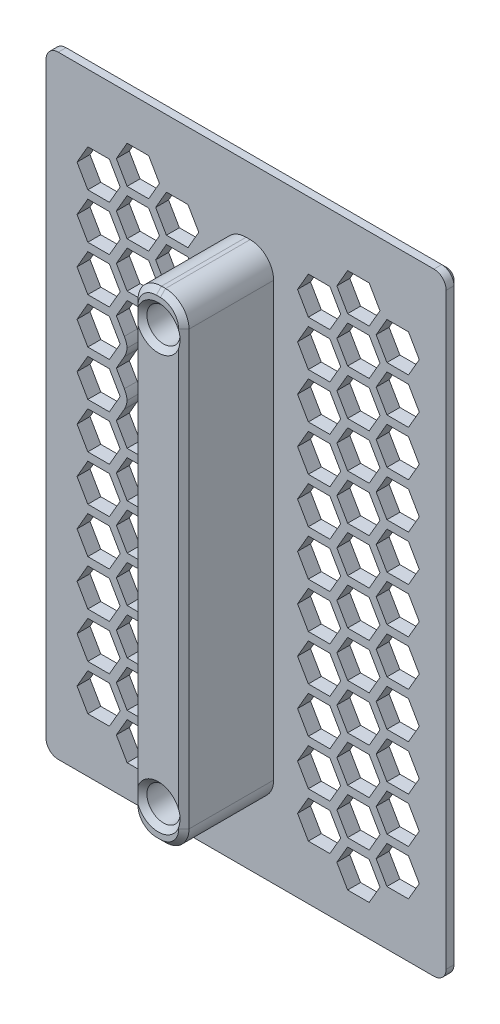
SolidWorks part; units mm, degrees
ref_plane "Front Plane" through (0, 0, 0) normal (0, 0, 1) x (1, 0, 0)
ref_plane "Top Plane" through (0, 0, 0) normal (0, 1, 0) x (1, 0, 0)
ref_plane "Right Plane" through (0, 0, 0) normal (1, 0, 0) x (0, 0, -1)
sketch "Sketch1" plane through (0, 0, 0) normal (0, 0, 1) x (1, 0, 0)
  line L0 (24.5, 37.5) -> (-24.5, 37.5) construction
  line L1 (24.5, -37.5) -> (-24.5, -37.5)
  line L2 (24.5, -37.5) -> (24.5, 37.5)
  line L3 (24.5, 37.5) -> (-24.5, 37.5)
  line L4 (-24.5, -37.5) -> (-24.5, 37.5)
  line L5 (24.5, -37.5) -> (-24.5, 37.5) construction
  line L6 (24.5, 37.5) -> (-24.5, -37.5) construction
  line L7 (24.5, 37.5) -> (24.5, -37.5) construction
  point P0 (0, 0)
extrude "Boss-Extrude1" add sketch "Sketch1" along normal blind 1.5875
sketch "Sketch2" plane through (0, 0, 1.5875) normal (0, 0, 1) x (1, 0, 0)
  line L12 (0.5, 29.5) -> (0, 29.5) construction
  line L13 (-3, 26.5) -> (-3, -26.5) construction
  line L14 (3.5, -26.5) -> (3.5, 26.5) construction
  line L15 (0, -29.5) -> (0.5, -29.5) construction
  line L16 (0.5, 29.5) -> (0, 29.5)
  line L17 (-3, 26.5) -> (-3, -26.5)
  line L18 (3.5, -26.5) -> (3.5, 26.5)
  line L19 (0, -29.5) -> (0.5, -29.5)
  line L20 (-2.873, 26.5) -> (-2.873, -26.5)
  line L21 (0, -29.373) -> (0.5, -29.373)
  line L22 (3.373, -26.5) -> (3.373, 26.5)
  line L23 (0.5, 29.373) -> (0, 29.373)
  arc A12 (3.5, 26.5) -> (0.5, 29.5) centre (0.5, 26.5) ccw construction
  arc A13 (0, 29.5) -> (-3, 26.5) centre (0, 26.5) ccw construction
  arc A14 (0.5, -29.5) -> (3.5, -26.5) centre (0.5, -26.5) ccw construction
  arc A15 (-3, -26.5) -> (0, -29.5) centre (0, -26.5) ccw construction
  arc A16 (3.5, 26.5) -> (0.5, 29.5) centre (0.5, 26.5) ccw
  arc A17 (0, 29.5) -> (-3, 26.5) centre (0, 26.5) ccw
  arc A18 (0.5, -29.5) -> (3.5, -26.5) centre (0.5, -26.5) ccw
  arc A19 (-3, -26.5) -> (0, -29.5) centre (0, -26.5) ccw
  arc A20 (0, 29.373) -> (-2.873, 26.5) centre (0, 26.5) ccw
  arc A21 (-2.873, -26.5) -> (0, -29.373) centre (0, -26.5) ccw
  arc A22 (0.5, -29.373) -> (3.373, -26.5) centre (0.5, -26.5) ccw
  arc A23 (3.373, 26.5) -> (0.5, 29.373) centre (0.5, 26.5) ccw
  dimension "D1" = 0.127
extrude "Boss-Extrude2" add sketch "Sketch2" along normal up to surface (11 mm away) contours L22 A23 L23 A20 L20 A21 L21 A22 region at (0.25, 0, 1.5875)
sketch "Sketch3" plane through (0, 0, 12.5875) normal (0, 0, 1) x (1, 0, 0)
  line L1 (0.25, 25.4) -> (0.25, -25.4) construction
  line L3 (-2.873, 0) -> (3.373, 0) construction
  line L4 (-2.873, -26.5) -> (-2.873, 26.5) construction
  line L5 (3.373, 26.5) -> (3.373, -26.5) construction
  circle A0 centre (0.25, 25.4) radius 2.032
  circle A1 centre (0.25, -25.4) radius 2.032
  point P13 (0.25, 0)
  dimension "D1" = 4.064
  dimension "D2" = 50.8
extrude "Cut-Extrude1" cut sketch "Sketch3" against normal blind 9.525
fillet "Fillet1" radius 1.5 4 edges at (24.5, -37.5, 0.7937) (-24.5, -37.5, 0.7937) (-24.5, 37.5, 0.7937) (24.5, 37.5, 0.7937)
sketch "Sketch4" plane through (0, 0, 0) normal (0, 0, -1) x (-1, 0, 0)
  line L0 (-18.5619, -28.5679) -> (-13.75, -31.346) construction
  line L1 (-16.3896, -31.346) -> (-15.0698, -33.632)
  line L2 (-15.0698, -33.632) -> (-12.4302, -33.632)
  line L3 (-12.4302, -33.632) -> (-11.1104, -31.346)
  line L4 (-11.1104, -31.346) -> (-12.4302, -29.06)
  line L5 (-12.4302, -29.06) -> (-15.0698, -29.06)
  line L6 (-15.0698, -29.06) -> (-16.3896, -31.346)
  line L7 (-21.2015, -28.5679) -> (-19.8817, -30.8539)
  line L8 (-19.8817, -30.8539) -> (-17.242, -30.8539)
  line L9 (-17.242, -30.8539) -> (-15.9222, -28.5679)
  line L10 (-15.9222, -28.5679) -> (-17.242, -26.2819)
  line L11 (-17.242, -26.2819) -> (-19.8817, -26.2819)
  line L12 (-19.8817, -26.2819) -> (-21.2015, -28.5679)
  line L13 (-10.258, -30.8539) -> (-7.6183, -30.8539)
  line L14 (-7.6183, -30.8539) -> (-6.2985, -28.5679)
  line L15 (-6.2985, -28.5679) -> (-7.6183, -26.2819)
  line L16 (-7.6183, -26.2819) -> (-10.258, -26.2819)
  line L17 (-10.258, -26.2819) -> (-11.5778, -28.5679)
  line L18 (-11.5778, -28.5679) -> (-10.258, -30.8539)
  line L19 (-11.1104, -31.346) -> (-10.258, -30.8539) construction
  line L20 (-13.75, -31.346) -> (-8.9381, -28.5679) construction
  line L21 (-4.5, -26.832) -> (-23, -26.832) construction
  line L22 (-10.258, -20.7257) -> (-11.5778, -23.0117)
  line L23 (-7.6183, -20.7257) -> (-10.258, -20.7257)
  line L24 (-6.2985, -23.0117) -> (-7.6183, -20.7257)
  line L25 (-7.6183, -25.2977) -> (-6.2985, -23.0117)
  line L26 (-10.258, -25.2977) -> (-7.6183, -25.2977)
  line L27 (-11.5778, -23.0117) -> (-10.258, -25.2977)
  line L28 (-11.1104, -25.7898) -> (-12.4302, -23.5038)
  line L29 (-12.4302, -23.5038) -> (-15.0698, -23.5038)
  line L30 (-15.0698, -23.5038) -> (-16.3896, -25.7898)
  line L31 (-16.3896, -25.7898) -> (-15.0698, -28.0758)
  line L32 (-15.0698, -28.0758) -> (-12.4302, -28.0758)
  line L33 (-12.4302, -28.0758) -> (-11.1104, -25.7898)
  line L34 (-17.242, -25.2977) -> (-15.9222, -23.0117)
  line L35 (-15.9222, -23.0117) -> (-17.242, -20.7257)
  line L36 (-17.242, -20.7257) -> (-19.8817, -20.7257)
  line L37 (-19.8817, -20.7257) -> (-21.2015, -23.0117)
  line L38 (-21.2015, -23.0117) -> (-19.8817, -25.2977)
  line L39 (-19.8817, -25.2977) -> (-17.242, -25.2977)
  line L40 (-10.258, -15.1694) -> (-11.5778, -17.4554)
  line L41 (-7.6183, -15.1694) -> (-10.258, -15.1694)
  line L42 (-6.2985, -17.4554) -> (-7.6183, -15.1694)
  line L43 (-7.6183, -19.7414) -> (-6.2985, -17.4554)
  line L44 (-10.258, -19.7414) -> (-7.6183, -19.7414)
  line L45 (-11.5778, -17.4554) -> (-10.258, -19.7414)
  line L46 (-11.1104, -20.2335) -> (-12.4302, -17.9475)
  line L47 (-12.4302, -17.9475) -> (-15.0698, -17.9475)
  line L48 (-15.0698, -17.9475) -> (-16.3896, -20.2335)
  line L49 (-16.3896, -20.2335) -> (-15.0698, -22.5195)
  line L50 (-15.0698, -22.5195) -> (-12.4302, -22.5195)
  line L51 (-12.4302, -22.5195) -> (-11.1104, -20.2335)
  line L52 (-17.242, -19.7414) -> (-15.9222, -17.4554)
  line L53 (-15.9222, -17.4554) -> (-17.242, -15.1694)
  line L54 (-17.242, -15.1694) -> (-19.8817, -15.1694)
  line L55 (-19.8817, -15.1694) -> (-21.2015, -17.4554)
  line L56 (-21.2015, -17.4554) -> (-19.8817, -19.7414)
  line L57 (-19.8817, -19.7414) -> (-17.242, -19.7414)
  line L58 (-10.258, -9.6132) -> (-11.5778, -11.8992)
  line L59 (-7.6183, -9.6132) -> (-10.258, -9.6132)
  line L60 (-6.2985, -11.8992) -> (-7.6183, -9.6132)
  line L61 (-7.6183, -14.1852) -> (-6.2985, -11.8992)
  line L62 (-10.258, -14.1852) -> (-7.6183, -14.1852)
  line L63 (-11.5778, -11.8992) -> (-10.258, -14.1852)
  line L64 (-11.1104, -14.6773) -> (-12.4302, -12.3913)
  line L65 (-12.4302, -12.3913) -> (-15.0698, -12.3913)
  line L66 (-15.0698, -12.3913) -> (-16.3896, -14.6773)
  line L67 (-16.3896, -14.6773) -> (-15.0698, -16.9633)
  line L68 (-15.0698, -16.9633) -> (-12.4302, -16.9633)
  line L69 (-12.4302, -16.9633) -> (-11.1104, -14.6773)
  line L70 (-17.242, -14.1852) -> (-15.9222, -11.8992)
  line L71 (-15.9222, -11.8992) -> (-17.242, -9.6132)
  line L72 (-17.242, -9.6132) -> (-19.8817, -9.6132)
  line L73 (-19.8817, -9.6132) -> (-21.2015, -11.8992)
  line L74 (-21.2015, -11.8992) -> (-19.8817, -14.1852)
  line L75 (-19.8817, -14.1852) -> (-17.242, -14.1852)
  line L76 (-10.258, -4.0569) -> (-11.5778, -6.3429)
  line L77 (-7.6183, -4.0569) -> (-10.258, -4.0569)
  line L78 (-6.2985, -6.3429) -> (-7.6183, -4.0569)
  line L79 (-7.6183, -8.6289) -> (-6.2985, -6.3429)
  line L80 (-10.258, -8.6289) -> (-7.6183, -8.6289)
  line L81 (-11.5778, -6.3429) -> (-10.258, -8.6289)
  line L82 (-11.1104, -9.121) -> (-12.4302, -6.835)
  line L83 (-12.4302, -6.835) -> (-15.0698, -6.835)
  line L84 (-15.0698, -6.835) -> (-16.3896, -9.121)
  line L85 (-16.3896, -9.121) -> (-15.0698, -11.407)
  line L86 (-15.0698, -11.407) -> (-12.4302, -11.407)
  line L87 (-12.4302, -11.407) -> (-11.1104, -9.121)
  line L88 (-17.242, -8.6289) -> (-15.9222, -6.3429)
  line L89 (-15.9222, -6.3429) -> (-17.242, -4.0569)
  line L90 (-17.242, -4.0569) -> (-19.8817, -4.0569)
  line L91 (-19.8817, -4.0569) -> (-21.2015, -6.3429)
  line L92 (-21.2015, -6.3429) -> (-19.8817, -8.6289)
  line L93 (-19.8817, -8.6289) -> (-17.242, -8.6289)
  line L94 (-10.258, 1.4993) -> (-11.5778, -0.7867)
  line L95 (-7.6183, 1.4993) -> (-10.258, 1.4993)
  line L96 (-6.2985, -0.7867) -> (-7.6183, 1.4993)
  line L97 (-7.6183, -3.0727) -> (-6.2985, -0.7867)
  line L98 (-10.258, -3.0727) -> (-7.6183, -3.0727)
  line L99 (-11.5778, -0.7867) -> (-10.258, -3.0727)
  line L100 (-11.1104, -3.5648) -> (-12.4302, -1.2788)
  line L101 (-12.4302, -1.2788) -> (-15.0698, -1.2788)
  line L102 (-15.0698, -1.2788) -> (-16.3896, -3.5648)
  line L103 (-16.3896, -3.5648) -> (-15.0698, -5.8508)
  line L104 (-15.0698, -5.8508) -> (-12.4302, -5.8508)
  line L105 (-12.4302, -5.8508) -> (-11.1104, -3.5648)
  line L106 (-17.242, -3.0727) -> (-15.9222, -0.7867)
  line L107 (-15.9222, -0.7867) -> (-17.242, 1.4993)
  line L108 (-17.242, 1.4993) -> (-19.8817, 1.4993)
  line L109 (-19.8817, 1.4993) -> (-21.2015, -0.7867)
  line L110 (-21.2015, -0.7867) -> (-19.8817, -3.0727)
  line L111 (-19.8817, -3.0727) -> (-17.242, -3.0727)
  line L112 (-10.258, 7.0556) -> (-11.5778, 4.7696)
  line L113 (-7.6183, 7.0556) -> (-10.258, 7.0556)
  line L114 (-6.2985, 4.7696) -> (-7.6183, 7.0556)
  line L115 (-7.6183, 2.4836) -> (-6.2985, 4.7696)
  line L116 (-10.258, 2.4836) -> (-7.6183, 2.4836)
  line L117 (-11.5778, 4.7696) -> (-10.258, 2.4836)
  line L118 (-11.1104, 1.9915) -> (-12.4302, 4.2775)
  line L119 (-12.4302, 4.2775) -> (-15.0698, 4.2775)
  line L120 (-15.0698, 4.2775) -> (-16.3896, 1.9915)
  line L121 (-16.3896, 1.9915) -> (-15.0698, -0.2945)
  line L122 (-15.0698, -0.2945) -> (-12.4302, -0.2945)
  line L123 (-12.4302, -0.2945) -> (-11.1104, 1.9915)
  line L124 (-17.242, 2.4836) -> (-15.9222, 4.7696)
  line L125 (-15.9222, 4.7696) -> (-17.242, 7.0556)
  line L126 (-17.242, 7.0556) -> (-19.8817, 7.0556)
  line L127 (-19.8817, 7.0556) -> (-21.2015, 4.7696)
  line L128 (-21.2015, 4.7696) -> (-19.8817, 2.4836)
  line L129 (-19.8817, 2.4836) -> (-17.242, 2.4836)
  line L130 (-10.258, 12.6118) -> (-11.5778, 10.3258)
  line L131 (-7.6183, 12.6118) -> (-10.258, 12.6118)
  line L132 (-6.2985, 10.3258) -> (-7.6183, 12.6118)
  line L133 (-7.6183, 8.0398) -> (-6.2985, 10.3258)
  line L134 (-10.258, 8.0398) -> (-7.6183, 8.0398)
  line L135 (-11.5778, 10.3258) -> (-10.258, 8.0398)
  line L136 (-11.1104, 7.5477) -> (-12.4302, 9.8337)
  line L137 (-12.4302, 9.8337) -> (-15.0698, 9.8337)
  line L138 (-15.0698, 9.8337) -> (-16.3896, 7.5477)
  line L139 (-16.3896, 7.5477) -> (-15.0698, 5.2617)
  line L140 (-15.0698, 5.2617) -> (-12.4302, 5.2617)
  line L141 (-12.4302, 5.2617) -> (-11.1104, 7.5477)
  line L142 (-17.242, 8.0398) -> (-15.9222, 10.3258)
  line L143 (-15.9222, 10.3258) -> (-17.242, 12.6118)
  line L144 (-17.242, 12.6118) -> (-19.8817, 12.6118)
  line L145 (-19.8817, 12.6118) -> (-21.2015, 10.3258)
  line L146 (-21.2015, 10.3258) -> (-19.8817, 8.0398)
  line L147 (-19.8817, 8.0398) -> (-17.242, 8.0398)
  line L148 (-10.258, 18.1681) -> (-11.5778, 15.8821)
  line L149 (-7.6183, 18.1681) -> (-10.258, 18.1681)
  line L150 (-6.2985, 15.8821) -> (-7.6183, 18.1681)
  line L151 (-7.6183, 13.5961) -> (-6.2985, 15.8821)
  line L152 (-10.258, 13.5961) -> (-7.6183, 13.5961)
  line L153 (-11.5778, 15.8821) -> (-10.258, 13.5961)
  line L154 (-11.1104, 13.104) -> (-12.4302, 15.39)
  line L155 (-12.4302, 15.39) -> (-15.0698, 15.39)
  line L156 (-15.0698, 15.39) -> (-16.3896, 13.104)
  line L157 (-16.3896, 13.104) -> (-15.0698, 10.818)
  line L158 (-15.0698, 10.818) -> (-12.4302, 10.818)
  line L159 (-12.4302, 10.818) -> (-11.1104, 13.104)
  line L160 (-17.242, 13.5961) -> (-15.9222, 15.8821)
  line L161 (-15.9222, 15.8821) -> (-17.242, 18.1681)
  line L162 (-17.242, 18.1681) -> (-19.8817, 18.1681)
  line L163 (-19.8817, 18.1681) -> (-21.2015, 15.8821)
  line L164 (-21.2015, 15.8821) -> (-19.8817, 13.5961)
  line L165 (-19.8817, 13.5961) -> (-17.242, 13.5961)
  line L166 (-10.258, 23.7243) -> (-11.5778, 21.4383)
  line L167 (-7.6183, 23.7243) -> (-10.258, 23.7243)
  line L168 (-6.2985, 21.4383) -> (-7.6183, 23.7243)
  line L169 (-7.6183, 19.1523) -> (-6.2985, 21.4383)
  line L170 (-10.258, 19.1523) -> (-7.6183, 19.1523)
  line L171 (-11.5778, 21.4383) -> (-10.258, 19.1523)
  line L172 (-11.1104, 18.6602) -> (-12.4302, 20.9462)
  line L173 (-12.4302, 20.9462) -> (-15.0698, 20.9462)
  line L174 (-15.0698, 20.9462) -> (-16.3896, 18.6602)
  line L175 (-16.3896, 18.6602) -> (-15.0698, 16.3742)
  line L176 (-15.0698, 16.3742) -> (-12.4302, 16.3742)
  line L177 (-12.4302, 16.3742) -> (-11.1104, 18.6602)
  line L178 (-17.242, 19.1523) -> (-15.9222, 21.4383)
  line L179 (-15.9222, 21.4383) -> (-17.242, 23.7243)
  line L180 (-17.242, 23.7243) -> (-19.8817, 23.7243)
  line L181 (-19.8817, 23.7243) -> (-21.2015, 21.4383)
  line L182 (-21.2015, 21.4383) -> (-19.8817, 19.1523)
  line L183 (-19.8817, 19.1523) -> (-17.242, 19.1523)
  line L202 (-11.5778, -28.5679) -> (-12.4302, -28.0758) construction
  line L203 (-0.25, 25.4) -> (-0.25, -25.4) construction
  line L204 (11.9302, 5.2617) -> (11.9302, 4.2775)
  line L205 (14.5698, 5.2617) -> (14.5698, 4.2775)
  line L206 (16.0821, 28.1376) -> (15.2297, 28.6297) construction
  line L207 (13.25, 27.4867) -> (13.25, 26.5025) construction
  line L208 (11.0778, -28.5679) -> (11.9302, -28.0758) construction
  line L209 (4, -26.832) -> (22.5, -26.832) construction
  line L410 (13.25, -31.346) -> (8.4381, -28.5679) construction
  line L419 (-10.258, 29.2806) -> (-11.5778, 26.9946)
  line L426 (-7.6183, 29.2806) -> (-10.258, 29.2806)
  line L427 (-6.2985, 26.9946) -> (-7.6183, 29.2806)
  line L434 (-7.6183, 24.7086) -> (-6.2985, 26.9946)
  line L441 (-4.5, -21.3426) -> (-4.5, -12.1527) construction
  line L442 (-23, -37.5) -> (-19.952, -37.5) construction
  line L443 (-23, -12.7255) -> (-23, -21.3426) construction
  line L444 (-10.258, 24.7086) -> (-7.6183, 24.7086)
  line L445 (-11.5778, 26.9946) -> (-10.258, 24.7086)
  line L446 (-11.1104, 24.2165) -> (-12.4302, 26.5025)
  line L447 (-12.4302, 26.5025) -> (-15.0698, 26.5025)
  line L448 (-15.0698, 26.5025) -> (-16.3896, 24.2165)
  line L449 (-16.3896, 24.2165) -> (-15.0698, 21.9305)
  line L450 (-15.0698, 21.9305) -> (-12.4302, 21.9305)
  line L451 (-12.4302, 21.9305) -> (-11.1104, 24.2165)
  line L452 (-17.242, 24.7086) -> (-15.9222, 26.9946)
  line L453 (-15.9222, 26.9946) -> (-17.242, 29.2806)
  line L454 (-17.242, 29.2806) -> (-19.8817, 29.2806)
  line L455 (-19.8817, 29.2806) -> (-21.2015, 26.9946)
  line L456 (-21.2015, 26.9946) -> (-19.8817, 24.7086)
  line L457 (-19.8817, 24.7086) -> (-17.242, 24.7086)
  line L477 (10.6104, -31.346) -> (9.758, -30.8539) construction
  line L489 (-13.75, 27.4867) -> (-13.75, 26.5025) construction
  line L491 (-16.5821, 28.1376) -> (-15.7297, 28.6297) construction
  line L492 (-11.1104, 29.7727) -> (-12.4302, 32.0587)
  line L493 (-12.4302, 32.0587) -> (-15.0698, 32.0587)
  line L494 (-15.0698, 32.0587) -> (-16.3896, 29.7727)
  line L495 (-16.3896, 29.7727) -> (-15.0698, 27.4867)
  line L496 (-15.0698, 27.4867) -> (-12.4302, 27.4867)
  line L497 (-12.4302, 27.4867) -> (-11.1104, 29.7727)
  line L498 (18.0619, -28.5679) -> (13.25, -31.346) construction
  line L505 (11.9302, 27.4867) -> (10.6104, 29.7727)
  line L533 (-0.25, 25.4) -> (-0.25, -25.4)
  line L534 (14.5698, 27.4867) -> (11.9302, 27.4867)
  line L535 (15.8896, 29.7727) -> (14.5698, 27.4867)
  line L536 (14.5698, 32.0587) -> (15.8896, 29.7727)
  line L537 (11.9302, 32.0587) -> (14.5698, 32.0587)
  line L538 (10.6104, 29.7727) -> (11.9302, 32.0587)
  line L539 (19.3817, 24.7086) -> (16.742, 24.7086)
  line L540 (20.7015, 26.9946) -> (19.3817, 24.7086)
  line L541 (19.3817, 29.2806) -> (20.7015, 26.9946)
  line L542 (16.742, 29.2806) -> (19.3817, 29.2806)
  line L543 (15.4222, 26.9946) -> (16.742, 29.2806)
  line L544 (16.742, 24.7086) -> (15.4222, 26.9946)
  line L545 (11.9302, 21.9305) -> (10.6104, 24.2165)
  line L546 (14.5698, 21.9305) -> (11.9302, 21.9305)
  line L547 (15.8896, 24.2165) -> (14.5698, 21.9305)
  line L548 (14.5698, 26.5025) -> (15.8896, 24.2165)
  line L549 (11.9302, 26.5025) -> (14.5698, 26.5025)
  line L550 (10.6104, 24.2165) -> (11.9302, 26.5025)
  line L551 (11.0778, 26.9946) -> (9.758, 24.7086)
  line L552 (9.758, 24.7086) -> (7.1183, 24.7086)
  line L553 (7.1183, 24.7086) -> (5.7985, 26.9946)
  line L554 (5.7985, 26.9946) -> (7.1183, 29.2806)
  line L555 (7.1183, 29.2806) -> (9.758, 29.2806)
  line L556 (9.758, 29.2806) -> (11.0778, 26.9946)
  line L557 (19.3817, 19.1523) -> (16.742, 19.1523)
  line L558 (20.7015, 21.4383) -> (19.3817, 19.1523)
  line L559 (19.3817, 23.7243) -> (20.7015, 21.4383)
  line L560 (16.742, 23.7243) -> (19.3817, 23.7243)
  line L561 (15.4222, 21.4383) -> (16.742, 23.7243)
  line L562 (16.742, 19.1523) -> (15.4222, 21.4383)
  line L563 (11.9302, 16.3742) -> (10.6104, 18.6602)
  line L564 (14.5698, 16.3742) -> (11.9302, 16.3742)
  line L565 (15.8896, 18.6602) -> (14.5698, 16.3742)
  line L566 (14.5698, 20.9462) -> (15.8896, 18.6602)
  line L567 (11.9302, 20.9462) -> (14.5698, 20.9462)
  line L568 (10.6104, 18.6602) -> (11.9302, 20.9462)
  line L569 (11.0778, 21.4383) -> (9.758, 19.1523)
  line L570 (9.758, 19.1523) -> (7.1183, 19.1523)
  line L571 (7.1183, 19.1523) -> (5.7985, 21.4383)
  line L572 (5.7985, 21.4383) -> (7.1183, 23.7243)
  line L573 (7.1183, 23.7243) -> (9.758, 23.7243)
  line L574 (9.758, 23.7243) -> (11.0778, 21.4383)
  line L575 (19.3817, 13.5961) -> (16.742, 13.5961)
  line L576 (20.7015, 15.8821) -> (19.3817, 13.5961)
  line L577 (19.3817, 18.1681) -> (20.7015, 15.8821)
  line L578 (16.742, 18.1681) -> (19.3817, 18.1681)
  line L579 (15.4222, 15.8821) -> (16.742, 18.1681)
  line L580 (16.742, 13.5961) -> (15.4222, 15.8821)
  line L581 (11.9302, 10.818) -> (10.6104, 13.104)
  line L582 (14.5698, 10.818) -> (11.9302, 10.818)
  line L583 (15.8896, 13.104) -> (14.5698, 10.818)
  line L584 (14.5698, 15.39) -> (15.8896, 13.104)
  line L585 (11.9302, 15.39) -> (14.5698, 15.39)
  line L586 (10.6104, 13.104) -> (11.9302, 15.39)
  line L587 (11.0778, 15.8821) -> (9.758, 13.5961)
  line L588 (9.758, 13.5961) -> (7.1183, 13.5961)
  line L589 (7.1183, 13.5961) -> (5.7985, 15.8821)
  line L590 (5.7985, 15.8821) -> (7.1183, 18.1681)
  line L591 (7.1183, 18.1681) -> (9.758, 18.1681)
  line L592 (9.758, 18.1681) -> (11.0778, 15.8821)
  line L593 (19.3817, 8.0398) -> (16.742, 8.0398)
  line L594 (20.7015, 10.3258) -> (19.3817, 8.0398)
  line L595 (19.3817, 12.6118) -> (20.7015, 10.3258)
  line L596 (16.742, 12.6118) -> (19.3817, 12.6118)
  line L597 (15.4222, 10.3258) -> (16.742, 12.6118)
  line L598 (16.742, 8.0398) -> (15.4222, 10.3258)
  line L599 (11.9302, 5.2617) -> (10.6104, 7.5477)
  line L600 (14.5698, 5.2617) -> (11.9302, 5.2617)
  line L601 (15.8896, 7.5477) -> (14.5698, 5.2617)
  line L602 (14.5698, 9.8337) -> (15.8896, 7.5477)
  line L603 (11.9302, 9.8337) -> (14.5698, 9.8337)
  line L604 (10.6104, 7.5477) -> (11.9302, 9.8337)
  line L605 (11.0778, 10.3258) -> (9.758, 8.0398)
  line L606 (9.758, 8.0398) -> (7.1183, 8.0398)
  line L607 (7.1183, 8.0398) -> (5.7985, 10.3258)
  line L608 (5.7985, 10.3258) -> (7.1183, 12.6118)
  line L609 (7.1183, 12.6118) -> (9.758, 12.6118)
  line L610 (9.758, 12.6118) -> (11.0778, 10.3258)
  line L611 (19.3817, 2.4836) -> (16.742, 2.4836)
  line L612 (20.7015, 4.7696) -> (19.3817, 2.4836)
  line L613 (19.3817, 7.0556) -> (20.7015, 4.7696)
  line L614 (16.742, 7.0556) -> (19.3817, 7.0556)
  line L615 (15.4222, 4.7696) -> (16.742, 7.0556)
  line L616 (16.742, 2.4836) -> (15.4222, 4.7696)
  line L617 (11.9302, -0.2945) -> (10.6104, 1.9915)
  line L618 (14.5698, -0.2945) -> (11.9302, -0.2945)
  line L619 (15.8896, 1.9915) -> (14.5698, -0.2945)
  line L620 (14.5698, 4.2775) -> (15.8896, 1.9915)
  line L621 (11.9302, 4.2775) -> (14.5698, 4.2775)
  line L622 (10.6104, 1.9915) -> (11.9302, 4.2775)
  line L623 (11.0778, 4.7696) -> (9.758, 2.4836)
  line L624 (9.758, 2.4836) -> (7.1183, 2.4836)
  line L625 (7.1183, 2.4836) -> (5.7985, 4.7696)
  line L626 (5.7985, 4.7696) -> (7.1183, 7.0556)
  line L627 (7.1183, 7.0556) -> (9.758, 7.0556)
  line L628 (9.758, 7.0556) -> (11.0778, 4.7696)
  line L629 (19.3817, -3.0727) -> (16.742, -3.0727)
  line L630 (20.7015, -0.7867) -> (19.3817, -3.0727)
  line L631 (19.3817, 1.4993) -> (20.7015, -0.7867)
  line L632 (16.742, 1.4993) -> (19.3817, 1.4993)
  line L633 (15.4222, -0.7867) -> (16.742, 1.4993)
  line L634 (16.742, -3.0727) -> (15.4222, -0.7867)
  line L635 (11.9302, -5.8508) -> (10.6104, -3.5648)
  line L636 (14.5698, -5.8508) -> (11.9302, -5.8508)
  line L637 (15.8896, -3.5648) -> (14.5698, -5.8508)
  line L638 (14.5698, -1.2788) -> (15.8896, -3.5648)
  line L639 (11.9302, -1.2788) -> (14.5698, -1.2788)
  line L640 (10.6104, -3.5648) -> (11.9302, -1.2788)
  line L641 (11.0778, -0.7867) -> (9.758, -3.0727)
  line L642 (9.758, -3.0727) -> (7.1183, -3.0727)
  line L643 (7.1183, -3.0727) -> (5.7985, -0.7867)
  line L644 (5.7985, -0.7867) -> (7.1183, 1.4993)
  line L645 (7.1183, 1.4993) -> (9.758, 1.4993)
  line L646 (9.758, 1.4993) -> (11.0778, -0.7867)
  line L647 (19.3817, -8.6289) -> (16.742, -8.6289)
  line L648 (20.7015, -6.3429) -> (19.3817, -8.6289)
  line L649 (19.3817, -4.0569) -> (20.7015, -6.3429)
  line L650 (16.742, -4.0569) -> (19.3817, -4.0569)
  line L651 (15.4222, -6.3429) -> (16.742, -4.0569)
  line L652 (16.742, -8.6289) -> (15.4222, -6.3429)
  line L653 (11.9302, -11.407) -> (10.6104, -9.121)
  line L654 (14.5698, -11.407) -> (11.9302, -11.407)
  line L655 (15.8896, -9.121) -> (14.5698, -11.407)
  line L656 (14.5698, -6.835) -> (15.8896, -9.121)
  line L657 (11.9302, -6.835) -> (14.5698, -6.835)
  line L658 (10.6104, -9.121) -> (11.9302, -6.835)
  line L659 (11.0778, -6.3429) -> (9.758, -8.6289)
  line L660 (9.758, -8.6289) -> (7.1183, -8.6289)
  line L661 (7.1183, -8.6289) -> (5.7985, -6.3429)
  line L662 (5.7985, -6.3429) -> (7.1183, -4.0569)
  line L663 (7.1183, -4.0569) -> (9.758, -4.0569)
  line L664 (9.758, -4.0569) -> (11.0778, -6.3429)
  line L665 (19.3817, -14.1852) -> (16.742, -14.1852)
  line L666 (20.7015, -11.8992) -> (19.3817, -14.1852)
  line L667 (19.3817, -9.6132) -> (20.7015, -11.8992)
  line L668 (16.742, -9.6132) -> (19.3817, -9.6132)
  line L669 (15.4222, -11.8992) -> (16.742, -9.6132)
  line L670 (16.742, -14.1852) -> (15.4222, -11.8992)
  line L671 (11.9302, -16.9633) -> (10.6104, -14.6773)
  line L672 (14.5698, -16.9633) -> (11.9302, -16.9633)
  line L673 (15.8896, -14.6773) -> (14.5698, -16.9633)
  line L674 (14.5698, -12.3913) -> (15.8896, -14.6773)
  line L675 (11.9302, -12.3913) -> (14.5698, -12.3913)
  line L676 (10.6104, -14.6773) -> (11.9302, -12.3913)
  line L677 (11.0778, -11.8992) -> (9.758, -14.1852)
  line L678 (9.758, -14.1852) -> (7.1183, -14.1852)
  line L679 (7.1183, -14.1852) -> (5.7985, -11.8992)
  line L680 (5.7985, -11.8992) -> (7.1183, -9.6132)
  line L681 (7.1183, -9.6132) -> (9.758, -9.6132)
  line L682 (9.758, -9.6132) -> (11.0778, -11.8992)
  line L683 (19.3817, -19.7414) -> (16.742, -19.7414)
  line L684 (20.7015, -17.4554) -> (19.3817, -19.7414)
  line L685 (19.3817, -15.1694) -> (20.7015, -17.4554)
  line L686 (16.742, -15.1694) -> (19.3817, -15.1694)
  line L687 (15.4222, -17.4554) -> (16.742, -15.1694)
  line L688 (16.742, -19.7414) -> (15.4222, -17.4554)
  line L689 (11.9302, -22.5195) -> (10.6104, -20.2335)
  line L690 (14.5698, -22.5195) -> (11.9302, -22.5195)
  line L691 (15.8896, -20.2335) -> (14.5698, -22.5195)
  line L692 (14.5698, -17.9475) -> (15.8896, -20.2335)
  line L693 (11.9302, -17.9475) -> (14.5698, -17.9475)
  line L694 (10.6104, -20.2335) -> (11.9302, -17.9475)
  line L695 (11.0778, -17.4554) -> (9.758, -19.7414)
  line L696 (9.758, -19.7414) -> (7.1183, -19.7414)
  line L697 (7.1183, -19.7414) -> (5.7985, -17.4554)
  line L698 (5.7985, -17.4554) -> (7.1183, -15.1694)
  line L699 (7.1183, -15.1694) -> (9.758, -15.1694)
  line L700 (9.758, -15.1694) -> (11.0778, -17.4554)
  line L701 (19.3817, -25.2977) -> (16.742, -25.2977)
  line L702 (20.7015, -23.0117) -> (19.3817, -25.2977)
  line L703 (19.3817, -20.7257) -> (20.7015, -23.0117)
  line L704 (16.742, -20.7257) -> (19.3817, -20.7257)
  line L705 (15.4222, -23.0117) -> (16.742, -20.7257)
  line L706 (16.742, -25.2977) -> (15.4222, -23.0117)
  line L707 (11.9302, -28.0758) -> (10.6104, -25.7898)
  line L708 (14.5698, -28.0758) -> (11.9302, -28.0758)
  line L709 (15.8896, -25.7898) -> (14.5698, -28.0758)
  line L710 (14.5698, -23.5038) -> (15.8896, -25.7898)
  line L711 (11.9302, -23.5038) -> (14.5698, -23.5038)
  line L712 (10.6104, -25.7898) -> (11.9302, -23.5038)
  line L713 (11.0778, -23.0117) -> (9.758, -25.2977)
  line L714 (9.758, -25.2977) -> (7.1183, -25.2977)
  line L715 (7.1183, -25.2977) -> (5.7985, -23.0117)
  line L716 (5.7985, -23.0117) -> (7.1183, -20.7257)
  line L717 (7.1183, -20.7257) -> (9.758, -20.7257)
  line L718 (9.758, -20.7257) -> (11.0778, -23.0117)
  line L719 (11.0778, -28.5679) -> (9.758, -30.8539)
  line L720 (9.758, -26.2819) -> (11.0778, -28.5679)
  line L721 (7.1183, -26.2819) -> (9.758, -26.2819)
  line L722 (5.7985, -28.5679) -> (7.1183, -26.2819)
  line L723 (7.1183, -30.8539) -> (5.7985, -28.5679)
  line L724 (9.758, -30.8539) -> (7.1183, -30.8539)
  line L725 (19.3817, -26.2819) -> (20.7015, -28.5679)
  line L726 (16.742, -26.2819) -> (19.3817, -26.2819)
  line L727 (15.4222, -28.5679) -> (16.742, -26.2819)
  line L728 (16.742, -30.8539) -> (15.4222, -28.5679)
  line L729 (19.3817, -30.8539) -> (16.742, -30.8539)
  line L730 (20.7015, -28.5679) -> (19.3817, -30.8539)
  line L731 (14.5698, -29.06) -> (15.8896, -31.346)
  line L732 (11.9302, -29.06) -> (14.5698, -29.06)
  line L733 (10.6104, -31.346) -> (11.9302, -29.06)
  line L734 (11.9302, -33.632) -> (10.6104, -31.346)
  line L735 (14.5698, -33.632) -> (11.9302, -33.632)
  line L736 (15.8896, -31.346) -> (14.5698, -33.632)
  line L737 (11.9302, 10.818) -> (11.9302, 9.8337)
  line L738 (14.5698, 10.818) -> (14.5698, 9.8337)
  circle A0 centre (-13.75, -31.346) radius 2.286 construction
  circle A1 centre (-18.5619, -28.5679) radius 2.286 construction
  circle A2 centre (-8.9381, -28.5679) radius 2.286 construction
  circle A11 centre (-13.75, 29.7727) radius 2.286 construction
  circle A12 centre (13.25, 29.7727) radius 2.286 construction
  circle A13 centre (8.4381, -28.5679) radius 2.286 construction
  circle A14 centre (18.0619, -28.5679) radius 2.286 construction
  circle A15 centre (13.25, -31.346) radius 2.286 construction
  point P28 (-13.75, -26.832)
  dimension "D1" = 4.572
  dimension "D2" = 5.5562
  dimension "D3" = 4.514
  dimension "D8" = 10.668
  dimension "D4" = 11
extrude "Cut-Extrude2" cut sketch "Sketch4" against normal up to next (1.5875 mm away) contours L204 L621 L205 L600 | L738 L582 L737 L603 | L51 L46 L47 L48 L49 L50 | L39 L34 L35 L36 L37 L38 | L12 L7 L8 L9 L10 L11 | L30 L31 L32 L33 L28 L29 | L6 L1 L2 L3 L4 L5 | L17 L18 L13 L14 L15 L16 | L27 L26 L25 L24 L23 L22 | L44 L43 L42 L41 L40 L45 | L68 L69 L64 L65 L66 L67 | L52 L53 L54 L55 L56 L57 | L62 L61 L60 L59 L58 L63 | L75 L70 L71 L72 L73 L74 | L86 L87 L82 L83 L84 L85 | L80 L79 L78 L77 L76 L81 | L104 L105 L100 L101 L102 L103 | L93 L88 L89 L90 L91 L92 | L111 L106 L107 L108 L109 L110 | L129 L124 L125 L126 L127 L128 | L122 L123 L118 L119 L120 L121 | L98 L97 L96 L95 L94 L99 | L116 L115 L114 L113 L112 L117 | L140 L141 L136 L137 L138 L139 | L147 L142 L143 L144 L145 L146 | L165 L160 L161 L162 L163 L164 | L183 L178 L179 L180 L181 L182 | L457 L452 L453 L454 L455 L456 | L496 L497 L492 L493 L494 L495 | L447 L448 L449 L450 L451 L446 | L426 L419 L445 L444 L434 L427 | L167 L166 L171 L170 L169 L168 | L173 L174 L175 L176 L177 L172 | L155 L156 L157 L158 L159 L154 | L149 L148 L153 L152 L151 L150 | L131 L130 L135 L134 L133 L132 | L555 L556 L551 L552 L553 L554 | L539 L544 L543 L542 L541 L540 | L535 L534 L505 L538 L537 L536 | L548 L547 L546 L545 L550 L549 | L561 L560 L559 L558 L557 L562 | L570 L571 L572 L573 L574 L569 | L588 L589 L590 L591 L592 L587 | L564 L563 L568 L567 L566 L565 | L575 L580 L579 L578 L577 L576 | L582 L581 L586 L585 L584 L583 | L606 L607 L608 L609 L610 L605 | L600 L599 L604 L603 L602 L601 | L593 L598 L597 L596 L595 L594 | L624 L625 L626 L627 L628 L623 | L611 L616 L615 L614 L613 L612 | L618 L617 L622 L621 L620 L619 | L642 L643 L644 L645 L646 L641 | L636 L635 L640 L639 L638 L637 | L629 L634 L633 L632 L631 L630 | L660 L661 L662 L663 L664 L659 | L654 L653 L658 L657 L656 L655 | L647 L652 L651 L650 L649 L648 | L665 L670 L669 L668 L667 L666 | L678 L679 L680 L681 L682 L677 | L672 L671 L676 L675 L674 L673 | L696 L697 L698 L699 L700 L695 | L690 L689 L694 L693 L692 L691 | L683 L688 L687 L686 L685 L684 | L704 L703 L702 L701 L706 L705 | L717 L718 L713 L714 L715 L716 | L711 L710 L709 L708 L707 L712 | L722 L721 L720 L719 L724 L723 | L735 L734 L733 L732 L731 L736 | L729 L728 L727 L726 L725 L730 region at (-13.25, 4.7696, 0) region at (-13.25, 10.3258, 0)
chamfer "Chamfer1" distance 0.635 angle 45 18 edges at (-24.5, 0, 0) (-24.0607, -37.0607, 0) (-24.0607, 37.0607, 0) (0, -37.5, 0) (0, 37.5, 0) (24.0607, -37.0607, 0) (24.0607, 37.0607, 0) (24.5, 0, 0) (2.282, -25.4, 12.5875) (2.282, 25.4, 12.5875) (-2.873, 0, 12.5875) (-2.0315, 28.5315, 12.5875) (-2.0315, -28.5315, 12.5875) (0.25, 29.373, 12.5875) (0.25, -29.373, 12.5875) (2.5315, 28.5315, 12.5875) (2.5315, -28.5315, 12.5875) (3.373, 0, 12.5875)
fillet "Fillet2" radius 2.54 8 edges at (-14.5698, 5.2617, 0.7938) (-14.5698, 4.2775, 0.7938) (-11.9302, 5.2617, 0.7938) (-11.9302, 4.2775, 0.7938) (-14.5698, 9.8337, 0.7938) (-14.5698, 10.818, 0.7938) (-11.9302, 10.818, 0.7938) (-11.9302, 9.8337, 0.7938)
